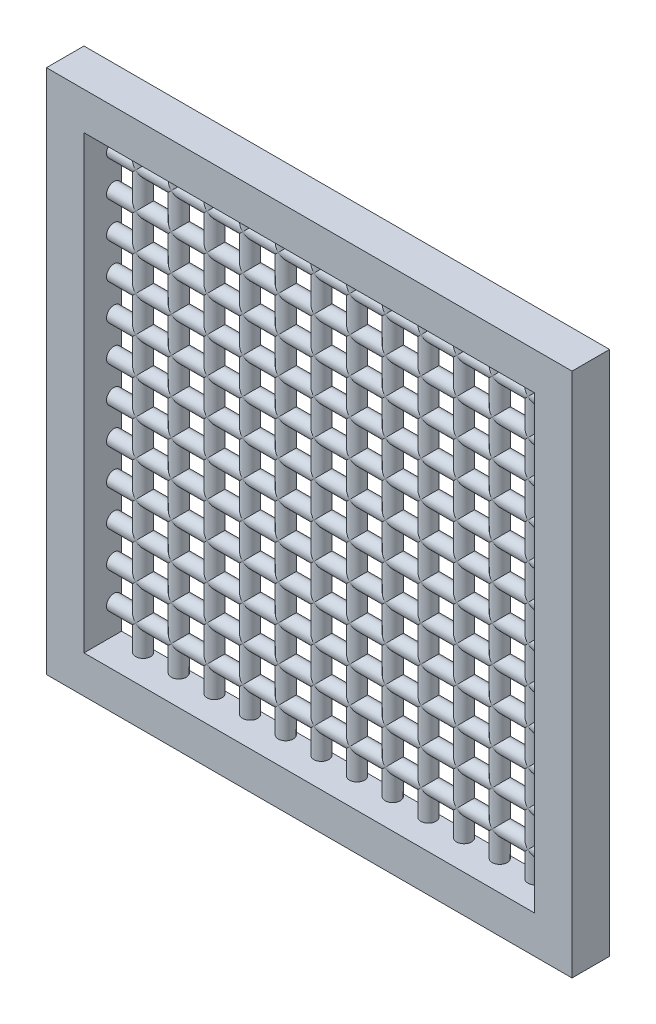
SolidWorks part; units mm, degrees
material "AISI 1010 Steel, hot rolled bar"
ref_plane "Front Plane" through (0, 0, 0) normal (0, 0, 1) x (1, 0, 0)
ref_plane "Top Plane" through (0, 0, 0) normal (0, 1, 0) x (1, 0, 0)
ref_plane "Right Plane" through (0, 0, 0) normal (1, 0, 0) x (0, 0, -1)
sketch "Sketch1" plane through (0, 0, 0) normal (0, 0, 1) x (1, 0, 0)
  line L0 (0, -27.94) -> (0, 27.94) construction
  line L1 (-152.4, -152.4) -> (152.4, -152.4)
  line L2 (-152.4, -152.4) -> (-152.4, 152.4)
  line L3 (-152.4, 152.4) -> (152.4, 152.4)
  line L4 (152.4, -152.4) -> (152.4, 152.4)
  line L5 (-152.4, -152.4) -> (152.4, 152.4) construction
  line L6 (-152.4, 152.4) -> (152.4, -152.4) construction
  line L8 (-177.8, -177.8) -> (177.8, -177.8)
  line L9 (-177.8, -177.8) -> (-177.8, 177.8)
  line L10 (-177.8, 177.8) -> (177.8, 177.8)
  line L11 (177.8, -177.8) -> (177.8, 177.8)
  line L12 (-177.8, -177.8) -> (177.8, 177.8) construction
  line L13 (-177.8, 177.8) -> (177.8, -177.8) construction
  point P0 (0, 0)
  point P9 (0, 0)
  dimension "D1" = 304.8
  dimension "D2" = 304.8
  dimension "D3" = 355.6
extrude "Boss-Extrude1" add sketch "Sketch1" along normal blind 25.4
ref_plane "Plane1" through (0, 0, 5.08) normal (0, 0, -1) x (-1, 0, 0)
sketch "Sketch3" plane through (0, 0, 5.08) normal (0, 0, -1) x (-1, 0, 0)
  line L0 (-152.4, 152.4) -> (152.4, 152.4) construction
  line L3 (-152.4, 132.715) -> (152.4, 132.715)
  line L4 (-152.4, -152.4) -> (-152.4, 152.4) construction
  line L5 (152.4, 152.4) -> (152.4, -152.4) construction
  dimension "D1" = 19.685
sketch "Sketch4" plane through (-152.4, 0, 0) normal (1, 0, 0) x (0, 0, -1)
  circle A0 centre (-5.08, 132.715) radius 5.08
  point P2 (-8.7738, 145.3039)
  point P4 (-5.08, 144.7275)
  dimension "D1" = 10.16
sweep "Sweep1" add profiles "Sketch4" path "Sketch3"
pattern_linear "LPattern1" count 12 spacing 24.13 along (0, -1, 0) of "Sweep1"
ref_point "Point2"
ref_axis "Axis1" through (0, 0, 25.4) along (0, 0, -1)
pattern_circular "CirPattern1" count 2 every 90 about axis through (0, 0, 25.4) along (0, 0, -1) of "Sweep1", "LPattern1"
